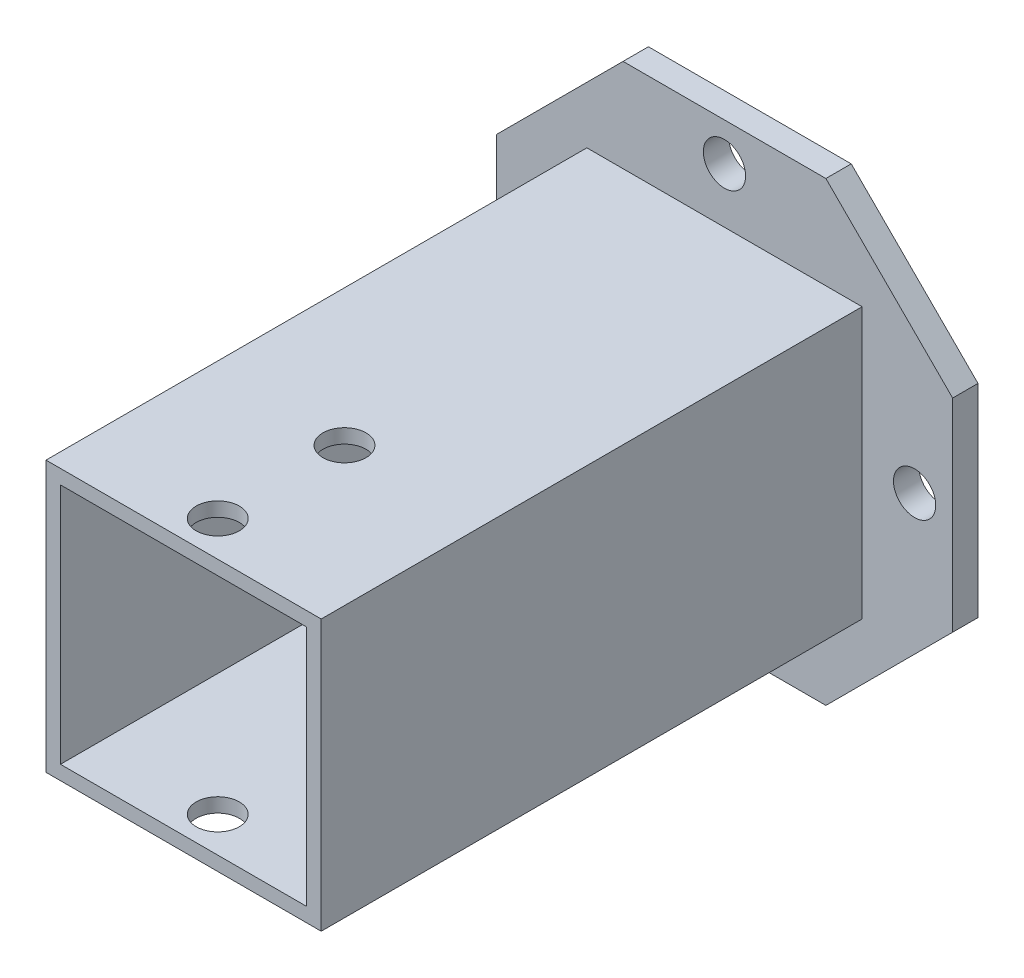
SolidWorks part; units mm, degrees
ref_plane "前视基准面" through (0, 0, 0) normal (0, 0, 1) x (1, 0, 0)
ref_plane "上视基准面" through (0, 0, 0) normal (0, 1, 0) x (1, 0, 0)
ref_plane "右视基准面" through (0, 0, 0) normal (1, 0, 0) x (0, 0, -1)
other "Configuration Table"
sketch "草图1" plane through (0, 0, 0) normal (0, 0, 1) x (1, 0, 0)
  line L1 (14.2, -14.2) -> (-14.2, -14.2)
  line L2 (14.2, -14.2) -> (14.2, 14.2)
  line L3 (14.2, 14.2) -> (-14.2, 14.2)
  line L4 (-14.2, -14.2) -> (-14.2, 14.2)
  line L5 (14.2, -14.2) -> (-14.2, 14.2) construction
  line L6 (14.2, 14.2) -> (-14.2, -14.2) construction
  point P0 (0, 0)
  dimension "D1" = 28.4
  dimension "D2" = 28.4
extrude "凸台-拉伸1" add sketch "草图1" along normal blind 3
sketch "草图2" plane through (0, 0, 3) normal (0, 0, 1) x (1, 0, 0)
  circle A0 centre (0, 0) radius 1
extrude "切除-拉伸1" cut sketch "草图2" against normal blind 3
sketch "草图5" plane through (0, 0, 0) normal (0, 0, -1) x (-1, 0, 0)
  circle A0 centre (0, 22.5) radius 2.5
  circle A1 centre (22.5, 0) radius 2.5
  circle A2 centre (-22.5, 0) radius 2.5
  circle A3 centre (0, -22.5) radius 2.5
sketch "草图6" plane through (0, 0, 3) normal (0, 0, 1) x (1, 0, 0)
  line L0 (12, 27) -> (27, 12)
  line L1 (27, -27) -> (-27, -27)
  line L2 (27, -27) -> (27, 27)
  line L3 (27, 27) -> (-27, 27)
  line L4 (-27, -27) -> (-27, 27)
  line L5 (27, -27) -> (-27, 27) construction
  line L6 (27, 27) -> (-27, -27) construction
  line L7 (27, -12) -> (12, -27)
  line L8 (-12, -27) -> (-27, -12)
  line L9 (-27, 12) -> (-12, 27)
  point P0 (0, 0)
  line M6 (-14.2, 14.2) -> (-14.2, -14.2)
  line M7 (-14.2, -14.2) -> (14.2, -14.2)
  line M8 (14.2, -14.2) -> (14.2, 14.2)
  line M9 (14.2, 14.2) -> (-14.2, 14.2)
  dimension "D1" = 4.5
  dimension "D2" = 15
  dimension "D3" = 15
  dimension "D4" = 15
  dimension "D5" = 15
  dimension "D6" = 15
  dimension "D7" = 15
  dimension "D8" = 15
  dimension "D9" = 15
extrude "凸台-拉伸3" add sketch "草图6" against normal blind 3 contours L9 L4 L8 L1 L7 L2 L0 L3 M6 M9 M8 M7 region at (18.96, 18.96, 3)
extrude "切除-拉伸2" cut sketch "草图5" against normal blind 3
sketch "草图7" plane through (0, 0, 3) normal (0, 0, 1) x (1, 0, 0)
  line L0 (14, -13) -> (14, 13)
  line L1 (13, 14) -> (-13.2829, 14)
  line L2 (13, 14) -> (-13.2829, 14) construction
  line L4 (13, -14) -> (-13.2829, -14)
  line L5 (-14.2829, -13) -> (-14.2829, 13)
  line L7 (-14.2829, -14) -> (14, -14)
  line L8 (-14.2829, -14) -> (-14.2829, 14)
  line L9 (-14.2829, 14) -> (14, 14)
  line L10 (14, -14) -> (14, 14)
  line L11 (16.2829, -16) -> (-16.2829, -16)
  line L12 (16.2829, -16) -> (16.2829, 16)
  line L13 (16.2829, 16) -> (-16.2829, 16)
  line L14 (-16.2829, -16) -> (-16.2829, 16)
  line L15 (16.2829, -16) -> (-16.2829, 16) construction
  line L16 (16.2829, 16) -> (-16.2829, -16) construction
  line L17 (14.5703, -14.3172) -> (-14.5703, -14.3172)
  line L18 (14.5703, -14.3172) -> (14.5703, 14.3172)
  line L19 (14.5703, 14.3172) -> (-14.5703, 14.3172)
  line L20 (-14.5703, -14.3172) -> (-14.5703, 14.3172)
  line L21 (14.5703, -14.3172) -> (-14.5703, 14.3172) construction
  line L22 (14.5703, 14.3172) -> (-14.5703, -14.3172) construction
  point P21 (0, 0)
  point P27 (0, 0)
  dimension "D1" = 2
  dimension "D2" = 2
extrude "凸台-拉伸4" add sketch "草图7" along normal blind 73 contours L14 L11 L12 L13 L17 L20 L19 L18 region at (0, -15.5434, 3)
sketch "草图8" plane through (-16.2829, 0, 0) normal (-1, 0, 0) x (0, 0, 1)
  line L0 (67, 16) -> (67, -16)
  line L1 (76, 16) -> (3, 16) construction
  line L2 (76, -16) -> (3, -16) construction
  line L4 (67, 16) -> (76, 16)
  line L5 (67, 16) -> (67, -16)
  line L6 (67, -16) -> (76, -16)
  line L7 (76, 16) -> (76, -16)
  line M2 (3, -16) -> (76, -16)
  line M3 (76, -16) -> (76, 16)
  line M4 (76, 16) -> (3, 16)
  dimension "D1" = 9
sketch "草图9" plane through (0, -16, 0) normal (0, -1, 0) x (1, 0, 0)
  circle A0 centre (-0.1414, 62.82) radius 2.55
  circle A1 centre (-0.1414, 47.82) radius 2.55
extrude "切除-拉伸3" cut sketch "草图8" against normal blind 73 contours L0 M4 M2 M3 region at (-16.2829, 0, 71.5)
extrude "切除-拉伸4" cut sketch "草图9" against normal blind 73
